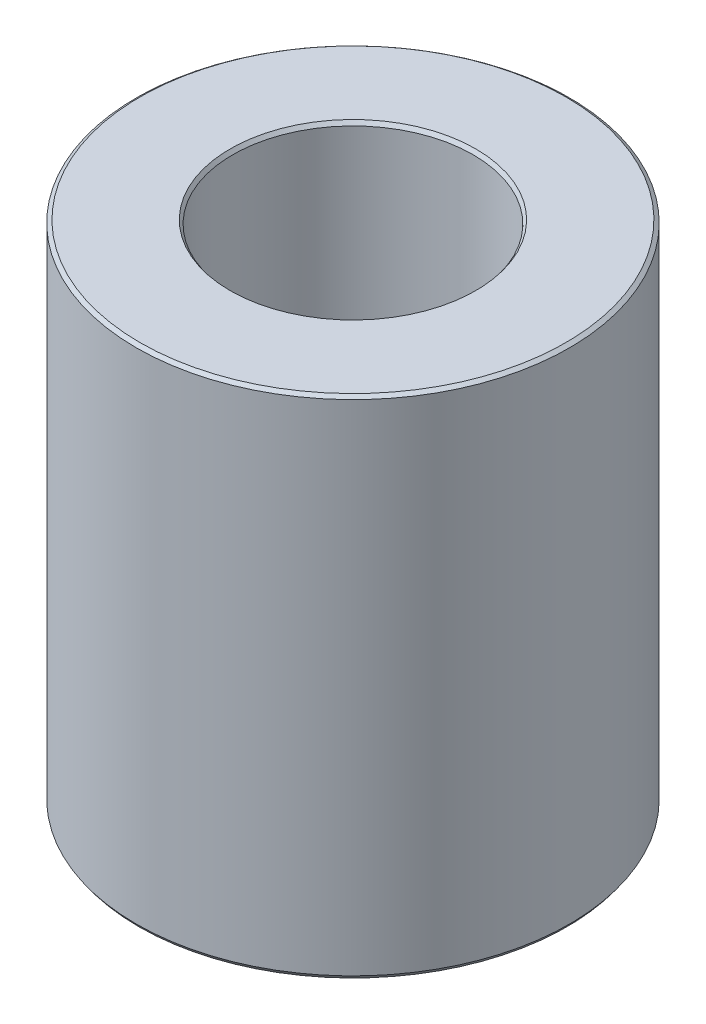
SolidWorks part; units mm, degrees
ref_plane "Front Plane" through (0, 0, 0) normal (0, 0, 1) x (1, 0, 0)
ref_plane "Top Plane" through (0, 0, 0) normal (0, 1, 0) x (1, 0, 0)
ref_plane "Right Plane" through (0, 0, 0) normal (1, 0, 0) x (0, 0, -1)
sketch "Sketch1" plane through (0, 0, 0) normal (0, 1, 0) x (1, 0, 0)
  circle A0 centre (0, 0) radius 42.5
  dimension "SLEEVE_OD" = 85
extrude "Boss-Extrude1" add sketch "Sketch1" along normal blind 99.1883
sketch "Sketch2" plane through (0, 0, 0) normal (0, 1, 0) x (1, 0, 0)
  circle A0 centre (0, 0) radius 23.5819
  dimension "BORE_D" = 47.1638
extrude "Cut-Extrude1" cut sketch "Sketch2" along normal through all
chamfer "Chamfer1" distance 0.5196 angle 54.502 4 edges at (0, 99.1883, 23.5819) (0, 0, 23.5819) (0, 0, 42.5) (0, 99.1883, 42.5) first distance on face at (0, 99.1883, 23.5819) first distance on face at (0, 0, 23.5819) first distance on face at (0, 99.1883, 42.5)
